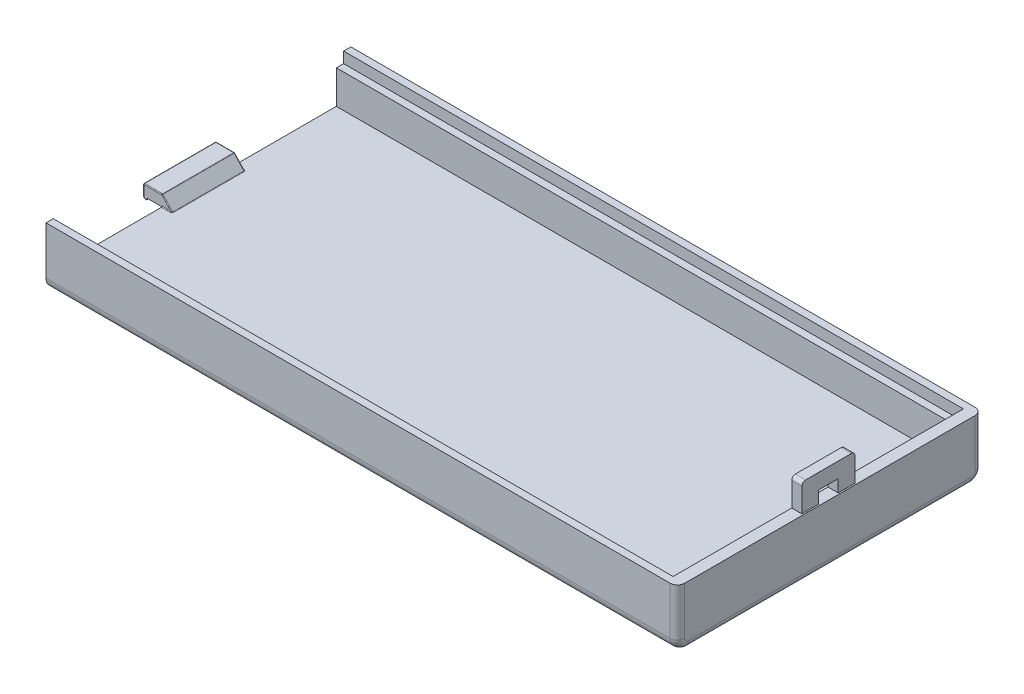
SolidWorks part; units mm, degrees
material "ABS"
ref_plane "Front Plane" through (0, 0, 0) normal (0, 0, 1) x (1, 0, 0)
ref_plane "Top Plane" through (0, 0, 0) normal (0, 1, 0) x (1, 0, 0)
ref_plane "Right Plane" through (0, 0, 0) normal (1, 0, 0) x (0, 0, -1)
sketch "Sketch1" plane through (0, 0, 0) normal (0, 1, 0) x (1, 0, 0)
  line L1 (-43.5, 21) -> (43.5, 21)
  line L2 (-43.5, 21) -> (-43.5, -21)
  line L3 (-43.5, -21) -> (43.5, -21)
  line L4 (43.5, 21) -> (43.5, -21)
  line L5 (-43.5, 21) -> (43.5, -21) construction
  line L6 (-43.5, -21) -> (43.5, 21) construction
  point P0 (0, 0)
  dimension "D1" = 42
  dimension "D2" = 87
extrude "BASE" add sketch "Sketch1" along normal blind 2
sketch "Sketch2" plane through (0, 2, 0) normal (0, 1, 0) x (1, 0, 0)
  line L0 (43.5, -21) -> (43.5, 21) construction
  line L1 (43.5, 19) -> (-43.5, 19)
  line L2 (43.5, 19) -> (43.5, 21)
  line L3 (43.5, 21) -> (-43.5, 21)
  line L4 (-43.5, 19) -> (-43.5, 21)
  dimension "D1" = 2
extrude "SIDE WALL" add sketch "Sketch2" along normal offset from surface (6.1 mm away) 8.1 up to face at (0, 0, 0)
sketch "Sketch5" plane through (-43.5, 0, 0) normal (-1, 0, 0) x (0, 0, 1)
  line L1 (-20, 6.6) -> (-19, 6.6)
  line L2 (-20, 6.6) -> (-20, 8.1)
  line L3 (-20, 8.1) -> (-19, 8.1)
  line L4 (-19, 6.6) -> (-19, 8.1)
  dimension "D1" = 1
  dimension "D2" = 1.5
extrude "TOP CUT SIDE WALL" cut sketch "Sketch5" against normal through all
mirror "SW M" about plane through (0, 0, 0) normal (0, 0, 1) of "TOP CUT SIDE WALL", "SIDE WALL"
sketch "Sketch4" plane through (0, 2, 0) normal (0, 1, 0) x (1, 0, 0)
  line L1 (43.5, 21) -> (41.9, 21)
  line L2 (43.5, 21) -> (43.5, -21)
  line L3 (43.5, -21) -> (41.9, -21)
  line L4 (41.9, 21) -> (41.9, -21)
  dimension "D1" = 1.6
extrude "REAR WALL" add sketch "Sketch4" along normal up to surface (6.1 mm away) up to face at (0, 8.1, 20.5)
sketch "Sketch6" plane through (0, 8.1, 0) normal (0, 1, 0) x (1, 0, 0)
  line L0 (41.9, 20) -> (41.9, -20) construction
  line L1 (41.9, -3.65) -> (43.3, -3.65)
  line L2 (41.9, -3.65) -> (41.9, 3.65)
  line L3 (41.9, 3.65) -> (43.3, 3.65)
  line L4 (43.3, -3.65) -> (43.3, 3.65)
  point P6 (41.9, 0)
  dimension "D1" = 7.3
  dimension "D2" = 1.4
extrude "REAR WALL TAB" add sketch "Sketch6" along normal blind 3.8
sketch "Sketch7" plane through (43.5, 0, 0) normal (1, 0, 0) x (0, 0, -1)
  line L0 (-3.65, 8.1) -> (3.65, 8.1) construction
  line L1 (-1.35, 9.8) -> (1.35, 9.8)
  line L2 (-1.35, 9.8) -> (-1.35, 8.1)
  line L3 (-1.35, 8.1) -> (1.35, 8.1)
  line L4 (1.35, 9.8) -> (1.35, 8.1)
  point P6 (0, 8.1)
  dimension "D1" = 2.7
  dimension "D2" = 1.7
extrude "RWT CUT" cut sketch "Sketch7" against normal through all
sketch "Sketch8" plane through (0, 0, 0) normal (0, 0, 1) x (1, 0, 0)
  line L0 (-42.1, 2) -> (-43.5, 3.5)
  line L1 (-43.5, 3.5) -> (-46.1, 3.5)
  line L2 (-46.1, 3.5) -> (-46.1, 2)
  line L3 (-46.1, 2) -> (-42.1, 2)
  line L4 (-43.5, 3.5) -> (-43.5, 2) construction
  dimension "D1" = 1.5
  dimension "D2" = 2.6
  dimension "D3" = 1.4
extrude "CASE LOCK" add sketch "Sketch8" along normal mid plane 10
sketch "Sketch10" plane through (0, 2, 0) normal (0, -1, 0) x (1, 0, 0)
  line L6 (-46.1, -5) -> (-43.5, -5) construction
  line L7 (-46.1, -5) -> (-45.5, -5)
  line L8 (-46.1, -5) -> (-46.1, 5)
  line L9 (-46.1, 5) -> (-45.5, 5)
  line L10 (-45.5, -5) -> (-45.5, 5)
  line L11 (-46.1, 5) -> (-43.5, 5) construction
  dimension "D1" = 0.6
extrude "CASE LOCK TAB" add sketch "Sketch10" along normal blind 0.3
fillet "F CLT" radius 0.3 2 edges at (-45.5, 1.7, 0) (-46.1, 1.7, 0)
fillet "F B" radius 1.5 2 edges at (0, 0, -21) (0, 0, 21)
fillet "F RW" radius 1 5 edges at (43.5, 4.8, 21) (43.5, 0.4393, 20.5607) (43.5, 4.8, -21) (43.5, 0.4393, -20.5607) (43.5, 0, 0)
fillet "F CL" radius 0.1 15 edges at (-42.8, 2, 5) (-42.8, 2, -5) (-42.1, 2, 0) (-42.8, 2.75, 5) (-42.8, 2.75, -5) (-43.5, 3.5, 0) (-44.8, 3.5, 5) (-46.1, 3.5, 0) (-44.8, 3.5, -5) (-45.5879, 1.7879, 5) (-46.0121, 1.7879, 5) (-45.5879, 1.7879, -5) (-46.0121, 1.7879, -5) (-46.1, 2.75, 5) (-46.1, 2.75, -5)
fillet "F RWT" radius 0.5 2 edges at (42.6, 11.9, -3.65) (42.6, 11.9, 3.65)
